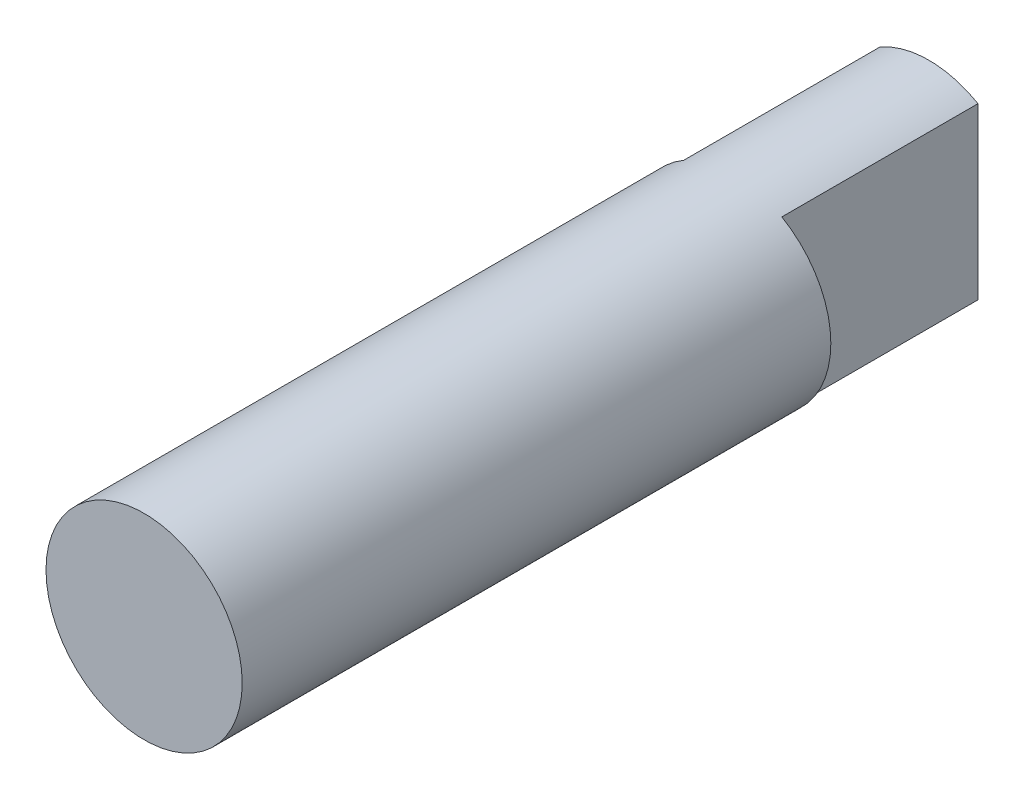
SolidWorks part; units mm, degrees
ref_plane "Front Plane" through (0, 0, 0) normal (0, 0, 1) x (1, 0, 0)
ref_plane "Top Plane" through (0, 0, 0) normal (0, 1, 0) x (1, 0, 0)
ref_plane "Right Plane" through (0, 0, 0) normal (1, 0, 0) x (0, 0, -1)
sketch "Sketch1" plane through (0, 0, 0) normal (0, 0, 1) x (1, 0, 0)
  circle A0 centre (0, 0) radius 12.7
  dimension "D1" = 25.4
extrude "Boss-Extrude1" add sketch "Sketch1" along normal blind 88.9 and the other way blind 12.7
sketch "Sketch2" plane through (0, 0, 0) normal (0, 1, 0) x (1, 0, 0)
  line L1 (12.7, 12.7) -> (6.35, 12.7)
  line L2 (12.7, 12.7) -> (12.7, -12.7)
  line L3 (12.7, -12.7) -> (6.35, -12.7)
  line L4 (6.35, 12.7) -> (6.35, -12.7)
  line L5 (-12.7, 12.7) -> (-6.35, 12.7)
  line L6 (-12.7, 12.7) -> (-12.7, -12.7)
  line L7 (-12.7, -12.7) -> (-6.35, -12.7)
  line L8 (-6.35, 12.7) -> (-6.35, -12.7)
  dimension "D1" = 25.4
  dimension "D2" = 6.35
extrude "Cut-Extrude1" cut sketch "Sketch2" against normal through all both and the other way through all
